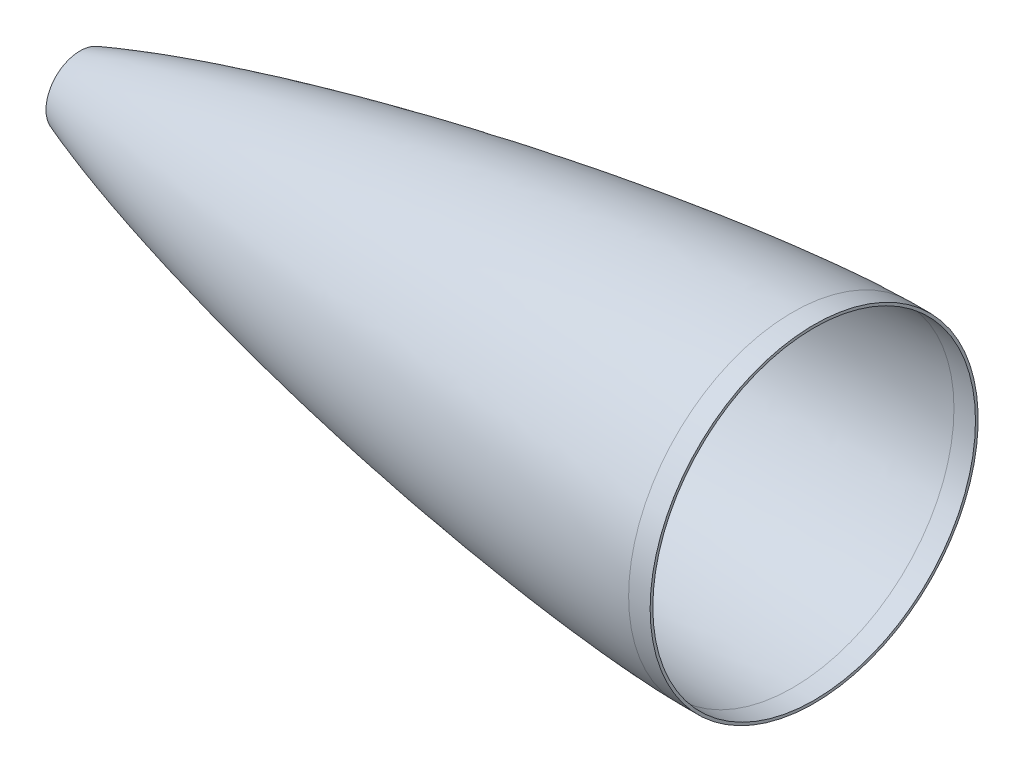
SolidWorks part; units mm, degrees
material "A-Glass Fiber"
ref_plane "Front Plane" through (0, 0, 0) normal (0, 0, 1) x (1, 0, 0)
ref_plane "Top Plane" through (0, 0, 0) normal (0, 1, 0) x (1, 0, 0)
ref_plane "Right Plane" through (0, 0, 0) normal (1, 0, 0) x (0, 0, -1)
sketch "Sketch1" plane through (0, 0, 0) normal (0, 0, 1) x (1, 0, 0)
  line L0 (0, 0) -> (457.2, 0) construction
  line L2 (457.2, 95.25) -> (457.2, 0) construction
  line L5 (457.2, 0) -> (469.8963, 0)
  line L7 (457.2, 95.25) -> (469.8963, 95.25)
  line L8 (469.8963, 0) -> (469.8963, 95.25) construction
  line L12 (457.1963, 96.8375) -> (471.4838, 96.8375) construction
  line L13 (457.1963, 96.8375) -> (469.8963, 96.8375)
  line L14 (469.8963, 96.8375) -> (469.8963, 95.25)
  line L15 (457.2, 0) -> (-1.613, 0) construction
  line L16 (471.4838, -1.5875) -> (471.4838, 96.8375) construction
  line L17 (457.2, 0) -> (0, 0) construction
  line L18 (457.2, -1.5875) -> (-1.8989, -1.5875) construction
  line L19 (457.2, -1.5875) -> (471.4838, -1.5875) construction
  line L20 (-1.613, 0) -> (0, 0)
  spline S0 degree 4 poles (0, 0) (0.0023, 0.0126) (0.0082, 0.0373) (0.0262, 0.085) (0.0706, 0.1767) (0.1354, 0.2842) (0.2204, 0.4066) (0.336, 0.5565) (0.5083, 0.7608) (0.8021, 1.0733) (1.3251, 1.5652) (2.2381, 2.3192) (3.8253, 3.4666) (6.614, 5.2253) (11.4561, 7.8766) (19.2936, 11.6017) (32.6156, 17.1305) (51.6883, 23.9819) (75.6131, 31.5462) (103.3102, 39.362) (131.8924, 46.6864) (160.6143, 53.4403) (189.4482, 59.6969) (218.3767, 65.4994) (247.3876, 70.874) (276.4727, 75.8318) (305.6259, 80.3722) (334.843, 84.4812) (364.1216, 88.1294) (389.7928, 90.8706) (411.8341, 92.8374) (428.9951, 94.0676) (440.0323, 94.6976) (448.6181, 95.062) (453.5214, 95.2002) (455.9737, 95.2443) (457.2, 95.25) knots 0 0 0 0 0 0.000108 0.000216 0.000433 0.000866 0.001175 0.001483 0.002044 0.003139 0.004822 0.007588 0.012112 0.019791 0.032854 0.05453 0.085907 0.142462 0.205216 0.267971 0.330725 0.393479 0.456233 0.518987 0.581741 0.644496 0.70725 0.770004 0.832758 0.895512 0.926889 0.958267 0.979133 0.989567 1 1 1 1 1 construction
  spline S1 degree 4 poles (0, 0) (0.0023, 0.0126) (0.0082, 0.0373) (0.0262, 0.085) (0.0706, 0.1767) (0.1354, 0.2842) (0.2204, 0.4066) (0.336, 0.5565) (0.5083, 0.7608) (0.8021, 1.0733) (1.3251, 1.5652) (2.2381, 2.3192) (3.8253, 3.4666) (6.614, 5.2253) (11.4561, 7.8766) (19.2936, 11.6017) (32.6156, 17.1305) (51.6883, 23.9819) (75.6131, 31.5462) (103.3102, 39.362) (131.8924, 46.6864) (160.6143, 53.4403) (189.4482, 59.6969) (218.3767, 65.4994) (247.3876, 70.874) (276.4727, 75.8318) (305.6259, 80.3722) (334.843, 84.4812) (364.1216, 88.1294) (389.7928, 90.8706) (411.8341, 92.8374) (428.9951, 94.0676) (440.0323, 94.6976) (448.6181, 95.062) (453.5214, 95.2002) (455.9737, 95.2443) (457.2, 95.25) knots 0 0 0 0 0 0.000108 0.000216 0.000433 0.000866 0.001175 0.001483 0.002044 0.003139 0.004822 0.007588 0.012112 0.019791 0.032854 0.05453 0.085907 0.142462 0.205216 0.267971 0.330725 0.393479 0.456233 0.518987 0.581741 0.644496 0.70725 0.770004 0.832758 0.895512 0.926889 0.958267 0.979133 0.989567 1 1 1 1 1
  spline S2 degree 1 poles (-1.8989, -1.5875) (457.1963, 96.8375) knots 0 0 1 1 construction
  spline S3 degree 3 poles (-1.8989, -1.5875) (-1.8716, -1.4358) (-1.8169, -1.1324) (-1.7486, -0.7532) (-1.694, -0.4498) (-1.6599, -0.2602) (-1.6326, -0.1085) (-1.6121, 0.0052) (-1.595, 0.1001) (-1.5814, 0.1758) (-1.5727, 0.2237) (-1.567, 0.2559) (-1.5636, 0.2739) (-1.5625, 0.2812) (-1.5411, 0.3918) (-1.5067, 0.5149) (-1.441, 0.6955) (-1.3886, 0.8061) (-1.3058, 0.9683) (-1.2132, 1.1209) (-1.0728, 1.3296) (-0.906, 1.5469) (-0.7105, 1.7767) (-0.5174, 1.9866) (-0.2609, 2.2487) (0.0592, 2.5515) (0.4443, 2.8898) (0.9608, 3.3175) (1.6111, 3.8178) (2.3999, 4.3829) (3.46, 5.0997) (4.801, 5.9446) (6.9705, 7.2185) (9.7204, 8.7026) (13.0595, 10.3683) (17.5542, 12.4746) (23.2313, 14.937) (30.1093, 17.7034) (37.0347, 20.3245) (43.9987, 22.8278) (53.3259, 26.0317) (65.0483, 29.8249) (79.1925, 34.1098) (93.3976, 38.1716) (107.6531, 42.042) (121.9511, 45.7433) (141.0645, 50.4743) (165.0378, 56.0378) (193.9118, 62.2237) (222.8767, 67.9595) (251.9217, 73.269) (281.0396, 78.1616) (310.2253, 82.6347) (339.4759, 86.6721) (368.79, 90.2401) (393.2717, 92.7732) (412.8919, 94.4772) (427.6244, 95.5657) (439.9241, 96.285) (449.7695, 96.6875) (454.7226, 96.8259) (457.1963, 96.8375) knots -0.004027 -0.004027 -0.004027 -0.004027 -0.003046 -0.002066 -0.001575 -0.001085 -0.00084 -0.000595 -0.00035 -0.000227 -0.000105 -0.000043 -0.000013 0.000003 0.000018 0.000079 0.000141 0.000263 0.000386 0.000631 0.000876 0.001366 0.001856 0.002347 0.002837 0.003817 0.004798 0.005778 0.007739 0.009701 0.011662 0.015584 0.019506 0.02735 0.035194 0.043038 0.058726 0.074414 0.090102 0.10579 0.121478 0.152854 0.18423 0.215606 0.246982 0.278358 0.309734 0.372486 0.435239 0.497991 0.560743 0.623495 0.686247 0.748999 0.811751 0.874504 0.90588 0.937256 0.968632 0.98432 1.000008 1.000008 1.000008 1.000008 only from (-1.613, 0) to (457.1963, 96.8375)
  dimension "D1" = 457.2
  dimension "D2" = 95.25
  dimension "D3" = 12.7
  dimension "D4" = 1.5875
revolve "Revolve3" add sketch "Sketch1" angle 360 about L0
ref_plane "Plane1" through (-1.613, 0, 0) normal (1, 0, 0) x (0, 0, -1)
sketch "Sketch2" plane through (-1.613, 0, 0) normal (1, 0, 0) x (0, 0, -1)
  circle A0 centre (0, 0) radius 96.8375 construction
  circle A1 centre (0, 0) radius 96.8375
extrude "Cut-Extrude1" cut sketch "Sketch2" along normal blind 38.1
